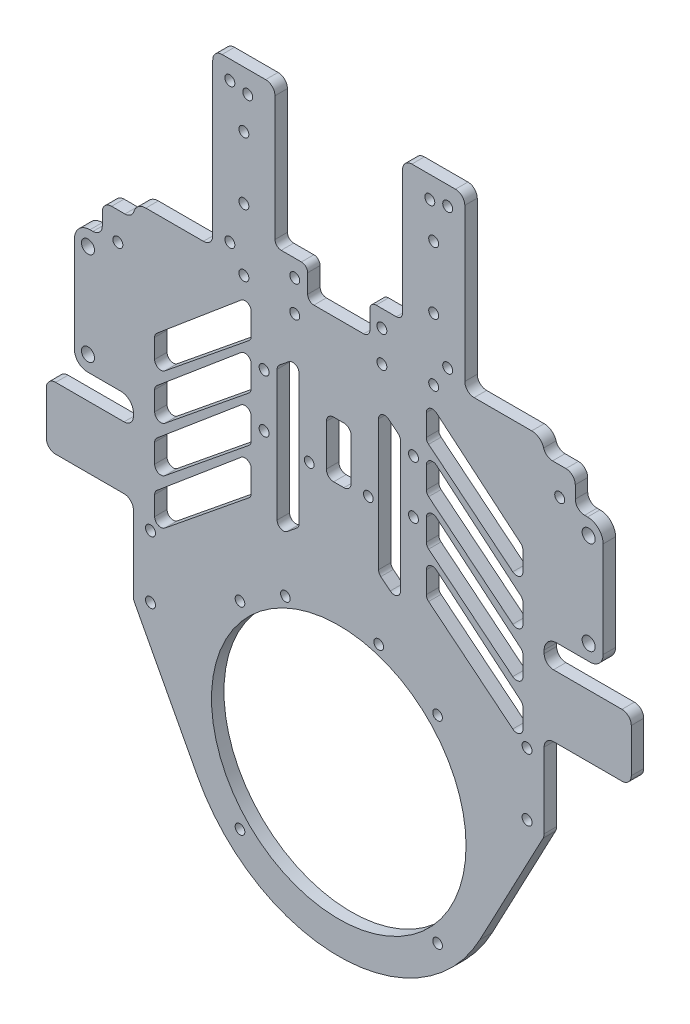
SolidWorks part; units mm, degrees
material "6061 合金"
ref_plane "前视基准面" through (0, 0, 0) normal (0, 0, 1) x (1, 0, 0)
ref_plane "上视基准面" through (0, 0, 0) normal (0, 1, 0) x (1, 0, 0)
ref_plane "右视基准面" through (0, 0, 0) normal (1, 0, 0) x (0, 0, -1)
sketch "草图1" plane through (0, 0, 0) normal (0, 0, 1) x (1, 0, 0)
  line L0 (-66, 126) -> (66, 126)
  line L1 (66, 126) -> (66, 15.1)
  line L2 (66, 15.1) -> (45.3153, -23.9831)
  line L3 (-45.3153, -23.9831) -> (-66, 15.1)
  line L4 (-66, 15.1) -> (-66, 126)
  line L5 (0, 143.651) -> (0, -77.7988) construction
  line L6 (-17.1531, 40.4102) -> (0, 0) construction
  line L7 (0, 0) -> (12.8351, 41.9818) construction
  line L8 (-31.7491, 31.7491) -> (0, 0) construction
  line L9 (-24.2152, 81.5) -> (25.2173, 81.5) construction
  line L10 (-29.945, 120.5) -> (27.106, 120.5) construction
  arc A0 (45.3153, -23.9831) -> (-45.3153, -23.9831) centre (0, 0) cw
  circle A1 centre (0, 0) radius 40.9
  circle A2 centre (0, 0) radius 44.9 construction
  circle A3 centre (-31.7491, 31.7491) radius 1.55
  circle A4 centre (-17.1531, 40.4102) radius 1.55
  circle A5 centre (12.8351, 41.9818) radius 1.55
  circle A6 centre (31.7491, 31.7491) radius 1.55
  circle A7 centre (31.7491, -31.7491) radius 1.55
  circle A8 centre (-31.7491, -31.7491) radius 1.55
  circle A9 centre (-9.5, 81.5) radius 1.55
  circle A10 centre (9.5, 81.5) radius 1.55
  circle A11 centre (-14.15, 120.5) radius 1.6
  circle A12 centre (13.85, 120.5) radius 1.6
  point P27 (0, 0)
  dimension "D3" = 81.8
  dimension "D4" = 89.8
  dimension "D7" = 17
  dimension "D11" = 3.1
  dimension "D14" = 63.4982
  dimension "D15" = 44.9
  dimension "D17" = 9.5
  dimension "D20" = 3.2
  dimension "D21" = 14.15
  dimension "D1" = 132
  dimension "D2" = 110.9
  dimension "D5" = 126
  dimension "D6" = 152.11
  dimension "D8" = 40
  dimension "D9" = 43.9
  dimension "D10" = 43.9
  dimension "D13" = 45
  dimension "D16" = 81.5
  dimension "D18" = 9.5
  dimension "D19" = 5.5
  dimension "D22" = 13.85
  dimension "D12" = 4
extrude "凸台-拉伸1" add sketch "草图1" along normal blind 4
sketch "草图2" plane through (0, 0, 4) normal (0, 0, 1) x (1, 0, 0)
  line L0 (-66, 111) -> (-79.95, 111)
  line L1 (-66, 126) -> (-66, 15.1) construction
  line L2 (-84.95, 106) -> (-84.95, 75.2)
  line L3 (-80.75, 71) -> (-66, 71)
  line L4 (-66, 71) -> (-66, 111)
  line L5 (0, 118.3019) -> (0, -51.4362) construction
  line L6 (66, 126) -> (-66, 126) construction
  line L7 (66, 71) -> (66, 111)
  line L8 (80.75, 71) -> (66, 71)
  line L9 (84.95, 106) -> (84.95, 75.2)
  line L10 (66, 111) -> (79.95, 111)
  circle A0 centre (-80.6, 106) radius 2.1
  circle A1 centre (-80.6, 76) radius 2.1
  arc A2 (-84.95, 106) -> (-79.95, 111) centre (-79.95, 106) cw
  arc A3 (-84.95, 75.2) -> (-80.75, 71) centre (-80.75, 75.2) ccw
  arc A4 (84.95, 75.2) -> (80.75, 71) centre (80.75, 75.2) cw
  arc A5 (84.95, 106) -> (79.95, 111) centre (79.95, 106) ccw
  circle A6 centre (80.3, 76) radius 2.1
  circle A7 centre (80.3, 106) radius 2.1
  point P18 (-84.95, 111)
  point P21 (-84.95, 71)
  point P34 (84.95, 71)
  point P35 (84.95, 111)
  dimension "D3" = 4.2
  dimension "D6" = 4.35
  dimension "D9" = 5
  dimension "D10" = 4.2
  dimension "D4" = 30
  dimension "D8" = 4.35
  dimension "D12" = 30
  dimension "D13" = 5
  dimension "D14" = 4.2
  dimension "D15" = 4.2
  dimension "D16" = 4.65
  dimension "D17" = 4.65
  dimension "D2" = 40
  dimension "D5" = 5
  dimension "D7" = 15
  dimension "D11" = 169.9
extrude "凸台-拉伸2" add sketch "草图2" against normal blind 4
sketch "草图3" plane through (0, 0, 4) normal (0, 0, 1) x (1, 0, 0)
  line L0 (0, 115.5232) -> (0, -53.75) construction
  line L13 (-4, 95.6433) -> (-4, 82.3567)
  line L14 (-1.6433, 80) -> (1.6433, 80)
  line L15 (4, 82.3567) -> (4, 95.6433)
  line L16 (1.6433, 98) -> (-1.6433, 98)
  line L32 (84.95, 75.2) -> (84.95, 106) construction
  line L33 (66, 126) -> (-66, 126) construction
  line L40 (-31.4189, 115.6719) -> (-58.4619, 92.9442)
  line L41 (-59.1752, 91.4131) -> (-59.1752, 85.2814)
  line L42 (-55.9148, 83.7285) -> (-28.8718, 105.6783)
  line L43 (-28.1322, 107.2311) -> (-28.1322, 114.1408)
  line L44 (-28.1322, 92.6485) -> (-28.1322, 99.5581)
  line L45 (-31.4189, 101.0892) -> (-58.4619, 78.3615)
  line L46 (-55.9148, 69.1458) -> (-28.8718, 91.0956)
  line L47 (-59.1752, 76.8304) -> (-59.1752, 70.6987)
  line L48 (-28.1322, 78.0658) -> (-28.1322, 84.9755)
  line L49 (-31.4189, 86.5065) -> (-58.4619, 63.7788)
  line L50 (-55.9148, 54.5632) -> (-28.8718, 76.5129)
  line L51 (-59.1752, 62.2477) -> (-59.1752, 56.116)
  line L52 (-28.1322, 63.4831) -> (-28.1322, 70.3928)
  line L53 (-31.4189, 71.9239) -> (-58.4619, 49.1961)
  line L54 (-55.9148, 39.9805) -> (-28.8718, 61.9302)
  line L55 (-59.1752, 47.665) -> (-59.1752, 41.5333)
  line L56 (-16.0321, 106.2463) -> (-19.0746, 103.7769)
  line L57 (-19.8142, 102.224) -> (-19.8142, 60.2677)
  line L58 (-16.5538, 58.7148) -> (-13.5113, 61.1843)
  line L59 (-12.7717, 62.7371) -> (-12.7717, 104.6934)
  line L60 (12.7717, 62.7371) -> (12.7717, 104.6934)
  line L61 (16.5538, 58.7148) -> (13.5113, 61.1843)
  line L62 (19.8142, 102.224) -> (19.8142, 60.2677)
  line L63 (16.0321, 106.2463) -> (19.0746, 103.7769)
  line L64 (59.1752, 47.665) -> (59.1752, 41.5333)
  line L65 (55.9148, 39.9805) -> (28.8718, 61.9302)
  line L66 (31.4189, 71.9239) -> (58.4619, 49.1961)
  line L67 (28.1322, 63.4831) -> (28.1322, 70.3928)
  line L68 (59.1752, 62.2477) -> (59.1752, 56.116)
  line L69 (55.9148, 54.5632) -> (28.8718, 76.5129)
  line L70 (31.4189, 86.5065) -> (58.4619, 63.7788)
  line L71 (28.1322, 78.0658) -> (28.1322, 84.9755)
  line L72 (59.1752, 76.8304) -> (59.1752, 70.6987)
  line L73 (55.9148, 69.1458) -> (28.8718, 91.0956)
  line L74 (31.4189, 101.0892) -> (58.4619, 78.3615)
  line L75 (28.1322, 92.6485) -> (28.1322, 99.5581)
  line L76 (28.1322, 107.2311) -> (28.1322, 114.1408)
  line L77 (55.9148, 83.7285) -> (28.8718, 105.6783)
  line L78 (59.1752, 91.4131) -> (59.1752, 85.2814)
  line L79 (31.4189, 115.6719) -> (58.4619, 92.9442)
  circle A9 centre (0, 0) radius 40.9 construction
  arc A10 (4, 95.6433) -> (1.6433, 98) centre (1.6433, 95.6433) ccw
  arc A11 (4, 82.3567) -> (1.6433, 80) centre (1.6433, 82.3567) cw
  arc A12 (-1.6433, 80) -> (-4, 82.3567) centre (-1.6433, 82.3567) cw
  arc A13 (-4, 95.6433) -> (-1.6433, 98) centre (-1.6433, 95.6433) cw
  arc A35 (-16.0321, 106.2463) -> (-12.7717, 104.6934) centre (-14.7717, 104.6934) cw
  arc A36 (-19.0746, 103.7769) -> (-19.8142, 102.224) centre (-17.8142, 102.224) ccw
  arc A37 (-13.5113, 61.1843) -> (-12.7717, 62.7371) centre (-14.7717, 62.7371) ccw
  arc A38 (-19.8142, 60.2677) -> (-16.5538, 58.7148) centre (-17.8142, 60.2677) ccw
  arc A39 (-55.9148, 39.9805) -> (-59.1752, 41.5333) centre (-57.1752, 41.5333) cw
  arc A40 (-58.4619, 49.1961) -> (-59.1752, 47.665) centre (-57.1752, 47.665) ccw
  arc A41 (-28.1322, 63.4831) -> (-28.8718, 61.9302) centre (-30.1322, 63.4831) cw
  arc A42 (-28.1322, 70.3928) -> (-31.4189, 71.9239) centre (-30.1322, 70.3928) ccw
  arc A43 (-55.9148, 54.5632) -> (-59.1752, 56.116) centre (-57.1752, 56.116) cw
  arc A44 (-58.4619, 63.7788) -> (-59.1752, 62.2477) centre (-57.1752, 62.2477) ccw
  arc A45 (-28.1322, 78.0658) -> (-28.8718, 76.5129) centre (-30.1322, 78.0658) cw
  arc A46 (-28.1322, 84.9755) -> (-31.4189, 86.5065) centre (-30.1322, 84.9755) ccw
  arc A47 (-58.4619, 78.3615) -> (-59.1752, 76.8304) centre (-57.1752, 76.8304) ccw
  arc A48 (-55.9148, 69.1458) -> (-59.1752, 70.6987) centre (-57.1752, 70.6987) cw
  arc A49 (-28.1322, 92.6485) -> (-28.8718, 91.0956) centre (-30.1322, 92.6485) cw
  arc A50 (-28.1322, 99.5581) -> (-31.4189, 101.0892) centre (-30.1322, 99.5581) ccw
  arc A51 (-59.1752, 85.2814) -> (-55.9148, 83.7285) centre (-57.1752, 85.2814) ccw
  arc A52 (-58.4619, 92.9442) -> (-59.1752, 91.4131) centre (-57.1752, 91.4131) ccw
  arc A53 (-28.8718, 105.6783) -> (-28.1322, 107.2311) centre (-30.1322, 107.2311) ccw
  arc A54 (-31.4189, 115.6719) -> (-28.1322, 114.1408) centre (-30.1322, 114.1408) cw
  arc A55 (31.4189, 115.6719) -> (28.1322, 114.1408) centre (30.1322, 114.1408) ccw
  arc A56 (28.8718, 105.6783) -> (28.1322, 107.2311) centre (30.1322, 107.2311) cw
  arc A57 (58.4619, 92.9442) -> (59.1752, 91.4131) centre (57.1752, 91.4131) cw
  arc A58 (59.1752, 85.2814) -> (55.9148, 83.7285) centre (57.1752, 85.2814) cw
  arc A59 (28.1322, 99.5581) -> (31.4189, 101.0892) centre (30.1322, 99.5581) cw
  arc A60 (28.1322, 92.6485) -> (28.8718, 91.0956) centre (30.1322, 92.6485) ccw
  arc A61 (55.9148, 69.1458) -> (59.1752, 70.6987) centre (57.1752, 70.6987) ccw
  arc A62 (58.4619, 78.3615) -> (59.1752, 76.8304) centre (57.1752, 76.8304) cw
  arc A63 (28.1322, 84.9755) -> (31.4189, 86.5065) centre (30.1322, 84.9755) cw
  arc A64 (28.1322, 78.0658) -> (28.8718, 76.5129) centre (30.1322, 78.0658) ccw
  arc A65 (58.4619, 63.7788) -> (59.1752, 62.2477) centre (57.1752, 62.2477) cw
  arc A66 (55.9148, 54.5632) -> (59.1752, 56.116) centre (57.1752, 56.116) ccw
  arc A67 (28.1322, 70.3928) -> (31.4189, 71.9239) centre (30.1322, 70.3928) cw
  arc A68 (28.1322, 63.4831) -> (28.8718, 61.9302) centre (30.1322, 63.4831) ccw
  arc A69 (58.4619, 49.1961) -> (59.1752, 47.665) centre (57.1752, 47.665) cw
  arc A70 (55.9148, 39.9805) -> (59.1752, 41.5333) centre (57.1752, 41.5333) ccw
  arc A71 (19.8142, 60.2677) -> (16.5538, 58.7148) centre (17.8142, 60.2677) cw
  arc A72 (13.5113, 61.1843) -> (12.7717, 62.7371) centre (14.7717, 62.7371) cw
  arc A73 (19.0746, 103.7769) -> (19.8142, 102.224) centre (17.8142, 102.224) cw
  arc A74 (16.0321, 106.2463) -> (12.7717, 104.6934) centre (14.7717, 104.6934) ccw
  dimension "D1" = 4
  dimension "D6" = 2.3567
  dimension "D7" = 2
  dimension "D2" = 4
  dimension "D3" = 4
  dimension "D4" = 18
  dimension "D5" = 80
extrude "切除-拉伸1" cut sketch "草图3" against normal blind 4
fillet "圆角1" radius 4 4 edges at (-66, 71, 2) (66, 71, 2) (66, 126, 2) (-66, 126, 2)
sketch "草图4" plane through (0, 0, 4) normal (0, 0, 1) x (1, 0, 0)
  line L0 (-10, 126) -> (-10, 119)
  line L1 (62, 126) -> (-62, 126) construction
  line L2 (-10, 119) -> (10, 119)
  line L3 (10, 119) -> (10, 126)
  line L4 (10, 126) -> (-10, 126)
  line L5 (66, 111) -> (66, 122) construction
  dimension "D1" = 7
  dimension "D2" = 20
  dimension "D3" = 56
extrude "切除-拉伸2" cut sketch "草图4" against normal through all
fillet "圆角2" radius 2 4 edges at (10, 126, 2) (-10, 126, 2) (-10, 119, 2) (10, 119, 2)
sketch "草图5" plane through (0, 0, 4) normal (0, 0, 1) x (1, 0, 0)
  line L0 (-40.5, 126) -> (-40.5, 181)
  line L1 (-12, 126) -> (-62, 126) construction
  line L2 (-40.5, 181) -> (-20.5, 181)
  line L3 (-20.5, 181) -> (-20.5, 126)
  line L4 (-40.5, 126) -> (-20.5, 126)
  line L5 (0, 172.5721) -> (0, 103.5745) construction
  line L10 (20.5, 126) -> (20.5, 181)
  line L11 (62, 126) -> (12, 126) construction
  line L12 (20.5, 181) -> (40.5, 181)
  line L13 (40.5, 181) -> (40.5, 126)
  line L14 (40.5, 126) -> (20.5, 126)
  dimension "D1" = 20
  dimension "D2" = 55
  dimension "D3" = 20.5
  dimension "D4" = 20
  dimension "D5" = 55
  dimension "D6" = 20.5
extrude "凸台-拉伸3" add sketch "草图5" against normal blind 4
sketch "草图6" plane through (0, 0, 4) normal (0, 0, 1) x (1, 0, 0)
  line L0 (-40.5, 181) -> (-40.5, 126) construction
  line L2 (0, 181.9353) -> (0, 128.2449) construction
  line L3 (-20.5, 181) -> (-40.5, 181) construction
  circle A0 centre (-29.75, 177) radius 1.65
  circle A1 centre (-29.75, 143.5) radius 1.65
  circle A4 centre (29.75, 143.5) radius 1.65
  circle A5 centre (29.75, 177) radius 1.65
  dimension "D1" = 3.3
  dimension "D2" = 10.75
  dimension "D4" = 4
  dimension "D3" = 33.5
fillet "圆角3" radius 3 4 edges at (40.5, 126, 2) (40.5, 181, 2) (-40.5, 126, 2) (-40.5, 181, 2)
sketch "草图7" plane through (0, 0, 4) normal (0, 0, 1) x (1, 0, 0)
  line L0 (0, 0) -> (0, 119) construction
  line L1 (-8, 119) -> (8, 119) construction
  line L2 (-30.5, 163) -> (-30.5, 130.7752) construction
  line L5 (-43.5, 126) -> (-62, 126) construction
  circle A0 centre (-30.5, 163) radius 1.6
  circle A1 centre (-30.5, 143) radius 1.6
  circle A2 centre (-30.5, 123) radius 1.6
  circle A3 centre (30.5, 163) radius 1.6
  circle A4 centre (30.5, 123) radius 1.6
  circle A5 centre (30.5, 143) radius 1.6
  dimension "D1" = 3.2
  dimension "D2" = 20
  dimension "D3" = 20
  dimension "D4" = 61
  dimension "D5" = 3
extrude "切除-拉伸4" cut sketch "草图7" against normal blind 10
sketch "草图8" plane through (0, 0, 4) normal (0, 0, 1) x (1, 0, 0)
  line L2 (24, 83) -> (-24, 83) construction
  line L3 (24, 83) -> (24, 100) construction
  line L4 (24, 100) -> (-24, 100) construction
  line L5 (-24, 83) -> (-24, 100) construction
  line L6 (24, 83) -> (-24, 100) construction
  line L7 (24, 100) -> (-24, 83) construction
  line L8 (37.5, 181) -> (20.5, 181) construction
  line L9 (0, 0) -> (0, 123.2843)
  circle A0 centre (-24, 100) radius 1.6
  circle A1 centre (24, 100) radius 1.6
  circle A2 centre (24, 83) radius 1.6
  circle A3 centre (-24, 83) radius 1.6
  point P0 (0, 91.5)
  dimension "D1" = 17
  dimension "D2" = 48
  dimension "D4" = 3.2
  dimension "D3" = 81
extrude "切除-拉伸7" cut sketch "草图8" against normal blind 24 contours A0 | A3 | A2 | A1 region at (-24, 100, 4) region at (24, 100, 4) region at (24, 83, 4) region at (-24, 83, 4)
sketch "草图9" plane through (0, 0, 4) normal (0, 0, 1) x (1, 0, 0)
  line L0 (0, 0) -> (0, 119) construction
  line L1 (66, 111) -> (76, 111)
  line L2 (66, 111) -> (66, 121)
  line L3 (66, 121) -> (76, 121)
  line L4 (76, 111) -> (76, 121)
  line L5 (-8, 119) -> (8, 119) construction
  line L6 (-66, 121) -> (-76, 121)
  line L7 (-76, 111) -> (-76, 121)
  line L8 (-66, 111) -> (-76, 111)
  line L9 (-66, 111) -> (-66, 121)
  dimension "D1" = 10
  dimension "D2" = 10
extrude "凸台-拉伸4" add sketch "草图9" against normal blind 4
fillet "圆角5" radius 3 6 edges at (-76, 111, 2) (-76, 121, 2) (-66, 121, 2) (66, 121, 2) (76, 121, 2) (76, 111, 2)
sketch "草图10" plane through (0, 0, 4) normal (0, 0, 1) x (1, 0, 0)
  line L0 (-76, 118) -> (-76, 114) construction
  line L1 (-68.7082, 121) -> (-73, 121) construction
  line L2 (0, 0) -> (0, 119) construction
  line L3 (-8, 119) -> (8, 119) construction
  circle A0 centre (-71, 112) radius 1.6
  circle A1 centre (71, 112) radius 1.6
  dimension "D1" = 3.2
  dimension "D2" = 5
  dimension "D3" = 9
extrude "切除-拉伸6" cut sketch "草图10" against normal blind 4
sketch "草图11" plane through (0, 0, 4) normal (0, 0, 1) x (1, 0, 0)
  line L0 (66, 15.1) -> (66, 67) construction
  line L1 (66, 63) -> (94, 63)
  line L2 (66, 63) -> (66, 43)
  line L3 (66, 43) -> (94, 43)
  line L4 (94, 63) -> (94, 43)
  line L5 (70, 71) -> (80.75, 71) construction
  line L6 (0, 27.3868) -> (0, -17.8221) construction
  line L7 (-66, 43) -> (-94, 43)
  line L8 (-66, 63) -> (-66, 43)
  line L9 (-66, 63) -> (-94, 63)
  line L10 (-94, 63) -> (-94, 43)
  dimension "D1" = 20
  dimension "D2" = 28
  dimension "D3" = 8
extrude "凸台-拉伸5" add sketch "草图11" against normal blind 4
fillet "圆角6" radius 3 12 edges at (-20.5, 181, 2) (20.5, 181, 2) (-94, 63, 2) (-94, 43, 2) (-66, 43, 2) (-66, 15.1, 2) (66, 15.1, 2) (66, 43, 2) (94, 43, 2) (94, 63, 2) (66, 63, 2) (-66, 63, 2)
sketch "草图13" plane through (0, 0, 4) normal (0, 0, 1) x (1, 0, 0)
  line L0 (-60.5, 152.6337) -> (-60.5, -37.2841) construction
  line L1 (-66, 40) -> (-66, 15.8449) construction
  line L2 (-91, 43) -> (-69, 43) construction
  line L3 (0, 166.4374) -> (0, -97.031) construction
  circle A0 centre (-60.5, 37) radius 1.6
  circle A1 centre (-60.5, 17) radius 1.6
  circle A2 centre (60.5, 17) radius 1.6
  circle A3 centre (60.5, 37) radius 1.6
  dimension "D2" = 3.2
  dimension "D3" = 20
  dimension "D4" = 6
  dimension "D1" = 5.5
extrude "切除-拉伸8" cut sketch "草图13" against normal blind 45
sketch "草图14" plane through (0, 0, 4) normal (0, 0, 1) x (1, 0, 0)
  line L0 (-23.5, 181) -> (-37.5, 181) construction
  line L1 (-40.5, 178) -> (-40.5, 129) construction
  line L2 (0, 181.7466) -> (0, 80.6903) construction
  circle A0 centre (-29.25, 174) radius 1.6
  circle A1 centre (29.25, 174) radius 1.6
  dimension "D1" = 3.2
  dimension "D2" = 7
  dimension "D3" = 11.25
extrude "切除-拉伸9" cut sketch "草图14" against normal blind 10
sketch "草图15" plane through (0, 0, 4) normal (0, 0, 1) x (1, 0, 0)
  line L0 (0, 152.5) -> (0, 0) construction
  line L1 (35, 130) -> (-35, 130) construction
  line L2 (35, 130) -> (35, 175) construction
  line L3 (35, 175) -> (-35, 175) construction
  line L4 (-35, 130) -> (-35, 175) construction
  line L5 (35, 130) -> (-35, 175) construction
  line L6 (35, 175) -> (-35, 130) construction
  line L7 (-23.5, 181) -> (-37.5, 181) construction
  circle A0 centre (-35, 175) radius 1.6
  circle A1 centre (35, 175) radius 1.6
  circle A2 centre (-35, 130) radius 1.6
  circle A3 centre (35, 130) radius 1.6
  point P0 (0, 152.5)
  dimension "D4" = 3.2
  dimension "D1" = 45
  dimension "D2" = 70
  dimension "D3" = 6
extrude "切除-拉伸10" cut sketch "草图15" against normal blind 10
sketch "草图16" plane through (0, 0, 4) normal (0, 0, 1) x (1, 0, 0)
  line L0 (-20.5, 136) -> (20.5, 136)
  line L1 (-14.15, 130.5) -> (-14.15, 120.5) construction
  line L2 (13.85, 120.5) -> (13.85, 130.5) construction
  line L35 (-20.5, 126) -> (-20.5, 178)
  line L36 (-23.5, 181) -> (-37.5, 181)
  line L37 (-40.5, 178) -> (-40.5, 129)
  line L38 (-43.5, 126) -> (-62, 126)
  line L39 (-68.7082, 121) -> (-73, 121)
  line L40 (-76, 118) -> (-76, 114)
  line L41 (-79, 111) -> (-79.95, 111)
  line L42 (-84.95, 106) -> (-84.95, 75.2)
  line L43 (-80.75, 71) -> (-70, 71)
  line L44 (-66, 67) -> (-66, 66)
  line L45 (-69, 63) -> (-91, 63)
  line L46 (-94, 60) -> (-94, 46)
  line L47 (-91, 43) -> (-69, 43)
  line L48 (-66, 40) -> (-66, 15.8449)
  line L49 (-65.6515, 14.4416) -> (-45.3153, -23.9831)
  line L50 (45.3153, -23.9831) -> (65.6515, 14.4416)
  line L51 (66, 15.8449) -> (66, 40)
  line L52 (69, 43) -> (91, 43)
  line L53 (94, 46) -> (94, 60)
  line L54 (91, 63) -> (69, 63)
  line L55 (66, 66) -> (66, 67)
  line L56 (70, 71) -> (80.75, 71)
  line L57 (84.95, 75.2) -> (84.95, 106)
  line L58 (79.95, 111) -> (79, 111)
  line L59 (76, 114) -> (76, 118)
  line L60 (73, 121) -> (68.7082, 121)
  line L61 (62, 126) -> (43.5, 126)
  line L62 (40.5, 129) -> (40.5, 178)
  line L63 (37.5, 181) -> (23.5, 181)
  line L64 (20.5, 178) -> (20.5, 126)
  line L65 (20.5, 126) -> (12, 126)
  line L66 (10, 124) -> (10, 121)
  line L67 (8, 119) -> (-8, 119)
  line L68 (-10, 121) -> (-10, 124)
  line L69 (-12, 126) -> (-20.5, 126)
  line L70 (-20.5, 126) -> (-20.5, 136)
  line L99 (20.5, 136) -> (20.5, 126)
  line L100 (20.5, 126) -> (12, 126)
  line L101 (10, 124) -> (10, 121)
  line L102 (8, 119) -> (-8, 119)
  line L103 (-10, 121) -> (-10, 124)
  line L104 (-12, 126) -> (-20.5, 126)
  circle A0 centre (-14.15, 130.5) radius 1.6
  circle A1 centre (13.85, 130.5) radius 1.6
  arc A35 (-20.5, 178) -> (-23.5, 181) centre (-23.5, 178) ccw
  arc A36 (-37.5, 181) -> (-40.5, 178) centre (-37.5, 178) ccw
  arc A37 (-43.5, 126) -> (-40.5, 129) centre (-43.5, 129) ccw
  arc A38 (-62, 126) -> (-65.8333, 123.1429) centre (-62, 122) ccw
  arc A39 (-68.7082, 121) -> (-65.8333, 123.1429) centre (-68.7082, 124) ccw
  arc A40 (-73, 121) -> (-76, 118) centre (-73, 118) ccw
  arc A41 (-79, 111) -> (-76, 114) centre (-79, 114) ccw
  arc A42 (-79.95, 111) -> (-84.95, 106) centre (-79.95, 106) ccw
  arc A43 (-84.95, 75.2) -> (-80.75, 71) centre (-80.75, 75.2) ccw
  arc A44 (-66, 67) -> (-70, 71) centre (-70, 67) ccw
  arc A45 (-69, 63) -> (-66, 66) centre (-69, 66) ccw
  arc A46 (-91, 63) -> (-94, 60) centre (-91, 60) ccw
  arc A47 (-94, 46) -> (-91, 43) centre (-91, 46) ccw
  arc A48 (-66, 40) -> (-69, 43) centre (-69, 40) ccw
  arc A49 (-66, 15.8449) -> (-65.6515, 14.4416) centre (-63, 15.8449) ccw
  arc A50 (-45.3153, -23.9831) -> (45.3153, -23.9831) centre (0, 0) ccw
  arc A51 (65.6515, 14.4416) -> (66, 15.8449) centre (63, 15.8449) ccw
  arc A52 (69, 43) -> (66, 40) centre (69, 40) ccw
  arc A53 (91, 43) -> (94, 46) centre (91, 46) ccw
  arc A54 (94, 60) -> (91, 63) centre (91, 60) ccw
  arc A55 (66, 66) -> (69, 63) centre (69, 66) ccw
  arc A56 (70, 71) -> (66, 67) centre (70, 67) ccw
  arc A57 (80.75, 71) -> (84.95, 75.2) centre (80.75, 75.2) ccw
  arc A58 (84.95, 106) -> (79.95, 111) centre (79.95, 106) ccw
  arc A59 (76, 114) -> (79, 111) centre (79, 114) ccw
  arc A60 (76, 118) -> (73, 121) centre (73, 118) ccw
  arc A61 (65.8333, 123.1429) -> (68.7082, 121) centre (68.7082, 124) ccw
  arc A62 (65.8333, 123.1429) -> (62, 126) centre (62, 122) ccw
  arc A63 (40.5, 129) -> (43.5, 126) centre (43.5, 129) ccw
  arc A64 (40.5, 178) -> (37.5, 181) centre (37.5, 178) ccw
  arc A65 (23.5, 181) -> (20.5, 178) centre (23.5, 178) ccw
  arc A66 (12, 126) -> (10, 124) centre (12, 124) ccw
  arc A67 (8, 119) -> (10, 121) centre (8, 121) ccw
  arc A68 (-10, 121) -> (-8, 119) centre (-8, 121) ccw
  arc A69 (-10, 124) -> (-12, 126) centre (-12, 124) ccw
  arc A101 (12, 126) -> (10, 124) centre (12, 124) ccw
  arc A102 (8, 119) -> (10, 121) centre (8, 121) ccw
  arc A103 (-10, 121) -> (-8, 119) centre (-8, 121) ccw
  arc A104 (-10, 124) -> (-12, 126) centre (-12, 124) ccw
  dimension "D3" = 3.2
  dimension "D4" = 3.2
  dimension "D5" = 10
  dimension "D2" = 17
  dimension "D6" = 10
  dimension "D1" = 0
extrude "凸台-拉伸6" add sketch "草图16" against normal blind 4
sketch "草图17" plane through (0, 0, 4) normal (0, 0, 1) x (1, 0, 0)
  line L0 (20.5, 136) -> (-20.5, 136) construction
  line L1 (10, 126) -> (-10, 126)
  line L2 (10, 126) -> (10, 136)
  line L3 (10, 136) -> (-10, 136)
  line L4 (-10, 126) -> (-10, 136)
  dimension "D1" = 20
  dimension "D2" = 10
  dimension "D3" = 10
extrude "切除-拉伸11" cut sketch "草图17" against normal blind 4
fillet "圆角7" radius 2 6 edges at (10, 126, 2) (-10, 126, 2) (-10, 136, 2) (20.5, 136, 2) (10, 136, 2) (-20.5, 136, 2)
